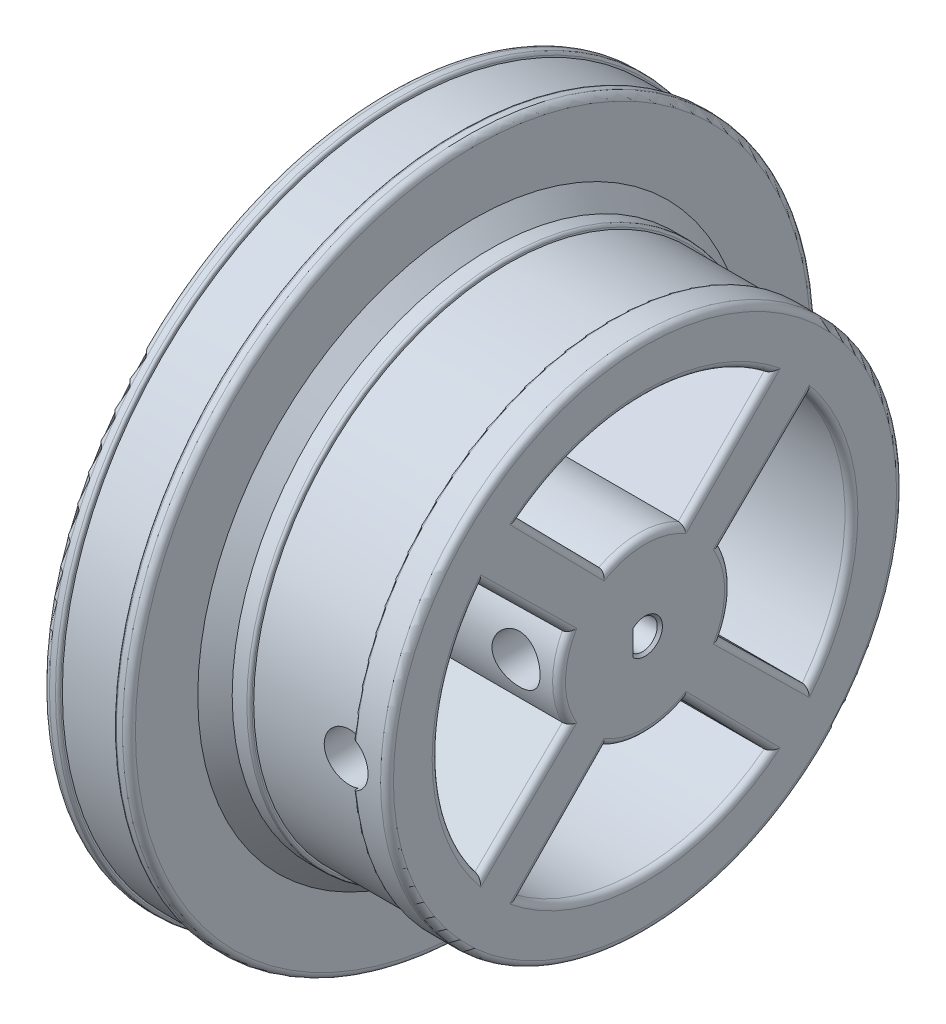
SolidWorks part; units mm, degrees
ref_plane "Front Plane" through (0, 0, 0) normal (0, 0, 1) x (1, 0, 0)
ref_plane "Top Plane" through (0, 0, 0) normal (0, 1, 0) x (1, 0, 0)
ref_plane "Right Plane" through (0, 0, 0) normal (1, 0, 0) x (0, 0, -1)
sketch "Sketch1" plane through (0, 0, 0) normal (1, 0, 0) x (0, 0, -1)
  circle A0 centre (0, 0) radius 40
  dimension "D1" = 80
extrude "Boss-Extrude1" add sketch "Sketch1" along normal blind 10 contours A0
sketch "Sketch2" plane through (10, 0, 0) normal (1, 0, 0) x (0, 0, -1)
  circle A0 centre (0, 0) radius 30
  dimension "D1" = 60
extrude "Boss-Extrude2" add sketch "Sketch2" along normal blind 20
sketch "Sketch5" plane through (30, 0, 0) normal (1, 0, 0) x (0, 0, -1)
  line L0 (-1.125, 1.3077) -> (-1.125, -1.3077)
  line L1 (1.725, -1.2522) -> (1.725, 1.7565) construction
  arc A0 (-1.125, -1.3077) -> (-1.125, 1.3077) centre (0, 0) ccw
  dimension "D1" = 3.45
  dimension "D2" = 2.85
extrude "Cut-Extrude1" cut sketch "Sketch5" against normal blind 12
sketch "Sketch6" plane through (30, 0, 0) normal (1, 0, 0) x (0, 0, -1)
  line L2 (4.624, 8.8667) -> (14.612, 19.0391)
  line L7 (4.2426, 0) -> (0, -4.2426) construction
  line L8 (4.2426, 0) -> (0, 4.2426) construction
  line L9 (0, 4.2426) -> (-4.2426, 0) construction
  line L13 (0, -4.2426) -> (-4.2426, 0) construction
  line L14 (4.2426, 0) -> (-4.2426, 0) construction
  line L15 (0, 4.2426) -> (0, -4.2426) construction
  line L16 (8.8667, 4.624) -> (19.0391, 14.612)
  line L17 (-8.8667, -4.624) -> (-19.0391, -14.612)
  line L18 (-4.624, -8.8667) -> (-14.612, -19.0391)
  line L19 (4.624, -8.8667) -> (14.612, -19.0391)
  line L20 (8.8667, -4.624) -> (19.0391, -14.612)
  line L21 (-4.624, 8.8667) -> (-14.612, 19.0391)
  line L22 (-8.8667, 4.624) -> (-19.0391, 14.612)
  arc A1 (14.612, 19.0391) -> (0, 24) centre (0, 0) ccw
  arc A2 (-2.9514, 23.8178) -> (-14.612, 19.0391) centre (0, 0) ccw
  arc A3 (19.0391, -14.612) -> (19.0391, 14.612) centre (0, 0) ccw
  arc A4 (-14.612, -19.0391) -> (14.612, -19.0391) centre (0, 0) ccw
  circle A5 centre (0, 0) radius 24.9521
  arc A6 (0, 24) -> (-2.9514, 23.8178) centre (0, 0) ccw
  arc A7 (-8.8667, 4.624) -> (-8.8667, -4.624) centre (0, 0) ccw
  arc A8 (4.624, 8.8667) -> (-4.624, 8.8667) centre (0, 0) ccw
  arc A9 (8.8667, -4.624) -> (8.8667, 4.624) centre (0, 0) ccw
  arc A10 (-4.624, -8.8667) -> (4.624, -8.8667) centre (0, 0) ccw
  arc A11 (-19.0391, 14.612) -> (-19.0391, -14.612) centre (0, 0) ccw
  dimension "D1" = 20
  dimension "D2" = 48
  dimension "D4" = 6
  dimension "D5" = 6
extrude "Cut-Extrude2" cut sketch "Sketch6" against normal up to next
ref_plane "Plane1" through (0, 0, 30) normal (0, 0, 1) x (1, 0, 0)
sketch "Sketch8" plane through (0, 0, 30) normal (0, 0, 1) x (1, 0, 0)
  line L0 (30, 0) -> (25, 0) construction
  line L1 (30, -30) -> (30, 30) construction
  line L2 (16.5, 0) -> (-16.5, 0) construction
  circle A0 centre (25, 0) radius 2.8
  dimension "D2" = 5.6
  dimension "D1" = 5
extrude "Cut-Extrude3" cut sketch "Sketch8" against normal blind 29.7 contours A0
chamfer "Chamfer1" distance 0.3 angle 45 2 edges at (30, 0, 1.125) (30, 0, -1.725)
sketch "Sketch9" plane through (0, 0, 0) normal (0, 0, 1) x (1, 0, 0)
  line L0 (10, 40) -> (0, 40) construction
  line L1 (0, -44) -> (0, 44) construction
  line L2 (1.75, 40) -> (8.25, 40)
  line L3 (8.25, 40) -> (8.25, 39.5)
  line L4 (5, 40) -> (5, 36.6496) construction
  line L5 (8.25, 39.5) -> (1.75, 39.5)
  line L6 (1.75, 40) -> (1.75, 39.5)
  line L7 (20, 30) -> (20, 25.6089) construction
  line L8 (30, 30) -> (10, 30) construction
  line L9 (14, 30) -> (26, 30)
  line L10 (26, 30) -> (26, 29.5)
  line L11 (26, 29.5) -> (14, 29.5)
  line L12 (14, 30) -> (14, 29.5)
  point P12 (5, 39.5)
  point P20 (20, 29.5)
  dimension "D1" = 3.25
  dimension "D2" = 0.5
  dimension "D3" = 6
  dimension "D4" = 0.5
ref_axis "X axis" through (31.5, 0, 0) along (-1, 0, 0)
revolve "Cut-Revolve2" cut sketch "Sketch9" angle 360 about axis through (31.5, 0, 0) along (-1, 0, 0)
chamfer "Chamfer2" distance 2 angle 45 1 edges at (10, 0, -30)
fillet "Fillet1" radius 0.75 17 edges at (30, -13.9529, -9.618) (30, -10, 0) (30, -13.9529, 9.618) (30, -24, 0) (30, 0, -24) (30, -9.618, -13.9529) (30, 0, -10) (30, 9.618, -13.9529) (30, 13.9529, -9.618) (30, 10, 0) (30, 24, 0) (30, 13.9529, 9.618) (30, 0, -30) (30, 9.618, 13.9529) (30, 0, 10) (30, -9.618, 13.9529) (30, 0, 24)
fillet "Fillet2" radius 0.3 4 edges at (26, 0, -30) (14, 0, -30) (8.25, 0, -40) (1.75, 0, -40)
fillet "Fillet3" radius 0.75 18 edges at (0, -13.9529, -9.618) (0, -24, 0) (0, -13.9529, 9.618) (0, -10, 0) (0, -9.618, 13.9529) (0, 0, 24) (0, 9.618, 13.9529) (0, 0, 10) (0, 0, -40) (0, 13.9529, 9.618) (0, 24, 0) (0, 13.9529, -9.618) (0, 10, 0) (0, 9.618, -13.9529) (0, 0, -24) (0, -9.618, -13.9529) (0, 0, -10) (10, 0, -40)
sketch "Sketch10" plane through (0, 0, 0) normal (-1, 0, 0) x (0, 0, 1)
  circle A0 centre (0, 0) radius 30 construction
  text T0 "'ey, dis mighty lissard man can swing his sword so fast, dat it's more dan da speed a sound!" font "Century Gothic" height 2.8
  dimension "D1" = 60
extrude "Cut-Extrude4" cut sketch "Sketch10" against normal blind 1
